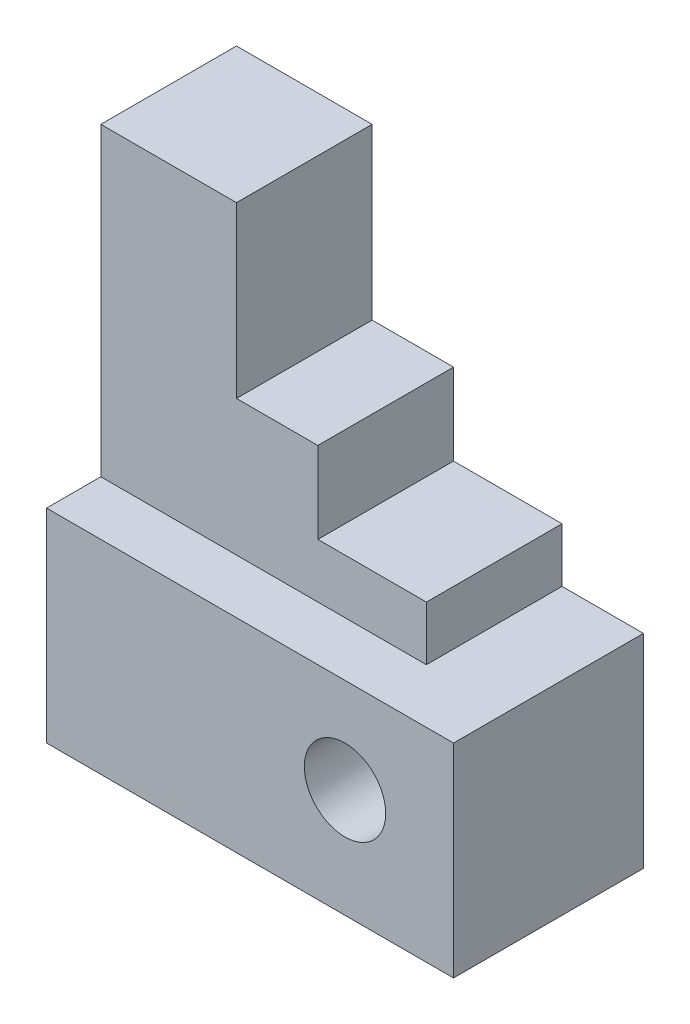
SolidWorks part; units mm, degrees
ref_plane "Front Plane" through (0, 0, 0) normal (0, 0, 1) x (1, 0, 0)
ref_plane "Top Plane" through (0, 0, 0) normal (0, 1, 0) x (1, 0, 0)
ref_plane "Right Plane" through (0, 0, 0) normal (1, 0, 0) x (0, 0, -1)
sketch "Sketch1" plane through (0, 0, 0) normal (0, 0, 1) x (1, 0, 0)
  line L0 (0, 30) -> (0, 75)
  line L1 (0, 0) -> (60, 0)
  line L2 (0, 0) -> (0, 30)
  line L3 (0, 30) -> (60, 30)
  line L4 (60, 0) -> (60, 30)
  line L5 (0, 75) -> (20, 75)
  line L6 (20, 75) -> (20, 50)
  line L7 (20, 50) -> (32, 50)
  line L8 (32, 50) -> (32, 38)
  line L9 (32, 38) -> (48, 38)
  line L10 (48, 38) -> (48, 30)
  circle A0 centre (44, 16) radius 6
  point P14 (50.266, 30)
  point P15 (44.0742, 41.4329)
  point P16 (44.2749, 14.1458)
  dimension "D11" = 12
  dimension "D1" = 30
  dimension "D2" = 60
  dimension "D3" = 75
  dimension "D4" = 20
  dimension "D5" = 12
  dimension "D6" = 20
  dimension "D7" = 12
  dimension "D8" = 12
  dimension "D9" = 16
  dimension "D10" = 16
extrude "Boss-Extrude1" add sketch "Sketch1" along normal blind 28 contours L1 L4 L3 L2 A0 region at (29.0614, 14.933, 0)
extrude "Boss-Extrude2" add sketch "Sketch1<3>" along normal blind 20 contours L10 L9 L8 L7 L6 L5 L0 L3 region at (16.0568, 48.2666, 0)
sketch "Sketch1<3>" plane through (0, 0, 0) normal (0, 0, 1) x (1, 0, 0) same geometry as "Sketch1"
